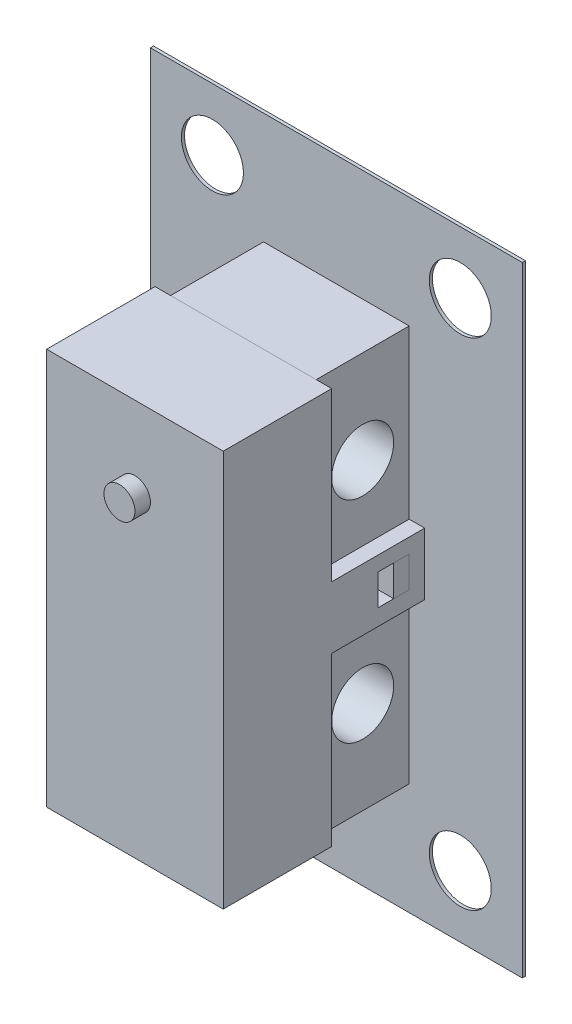
SolidWorks part; units mm, degrees
material "Plástico personalizado"
ref_plane "Alzado" through (0, 0, 0) normal (0, 0, 1) x (1, 0, 0)
ref_plane "Planta" through (0, 0, 0) normal (0, 1, 0) x (1, 0, 0)
ref_plane "Vista lateral" through (0, 0, 0) normal (1, 0, 0) x (0, 0, -1)
sketch "Sketch1" plane through (0, 0, 0) normal (0, 0, 1) x (1, 0, 0)
  line L1 (1.9718, 19.0836) -> (7.6718, 19.0836)
  line L2 (1.9718, 19.0836) -> (1.9718, 6.2836)
  line L3 (1.9718, 6.2836) -> (7.6718, 6.2836)
  line L4 (7.6718, 19.0836) -> (7.6718, 6.2836)
  dimension "D1" = 5.7
  dimension "D2" = 12.8
extrude "Boss-Extrude2" add sketch "Sketch1" along normal blind 6.5
sketch "Sketch3" plane through (0, 0, 6.5) normal (0, 0, 1) x (1, 0, 0)
  circle A0 centre (4.8218, 16.6018) radius 0.575
extrude "Boss-Extrude3" add sketch "Sketch3" along normal blind 0.5
sketch "Sketch7" plane through (7.6718, 0, 0) normal (1, 0, 0) x (0, 0, -1)
  line L0 (-6.5, 6.2836) -> (0, 6.2836) construction
  line L1 (0, 19.0836) -> (-3, 19.0836)
  line L2 (0, 19.0836) -> (0, 6.2836)
  line L3 (0, 6.2836) -> (-3, 6.2836)
  line L4 (-3, 19.0836) -> (-3, 6.2836)
  dimension "D1" = 3
extrude "Cut-Extrude1" cut sketch "Sketch7" against normal blind 0.5
sketch "Sketch8" plane through (1.9718, 0, 0) normal (-1, 0, 0) x (0, 0, 1)
  line L0 (6.5, 19.0836) -> (0, 19.0836) construction
  line L1 (0, 6.2836) -> (3, 6.2836)
  line L2 (0, 6.2836) -> (0, 19.0836)
  line L3 (0, 19.0836) -> (3, 19.0836)
  line L4 (3, 6.2836) -> (3, 19.0836)
  dimension "D1" = 3
extrude "Cut-Extrude2" cut sketch "Sketch8" against normal blind 0.5
sketch "Sketch9" plane through (7.1718, 0, 0) normal (1, 0, 0) x (0, 0, -1)
  line L0 (-3, 6.2836) -> (0, 6.2836) construction
  line L1 (0, 19.0836) -> (-3, 19.0836) construction
  circle A0 centre (-1.6614, 9.7836) radius 1
  circle A1 centre (-1.6614, 15.5836) radius 1
  dimension "D1" = 2
  dimension "D2" = 3.5
  dimension "D3" = 3.5
extrude "Cut-Extrude3" cut sketch "Sketch9" against normal through all
sketch "Sketch10" plane through (1.9718, 0, 0) normal (-1, 0, 0) x (0, 0, 1)
  line L0 (0, 12.6836) -> (6.5, 12.6836) construction
  line L1 (0, 19.0836) -> (0, 6.2836) construction
  line L2 (6.5, 19.0836) -> (6.5, 6.2836) construction
  line L3 (3, 6.2836) -> (3, 19.0836) construction
  line L4 (6, 11.6836) -> (0, 11.6836)
  line L5 (6, 11.6836) -> (6, 13.6836)
  line L6 (6, 13.6836) -> (0, 13.6836)
  line L7 (0, 11.6836) -> (0, 13.6836)
  line L8 (6, 11.6836) -> (0, 13.6836) construction
  line L9 (6, 13.6836) -> (0, 11.6836) construction
  point P6 (3, 12.6836)
  dimension "D1" = 2
extrude "Boss-Extrude4" add sketch "Sketch10" against normal blind 0.5
sketch "Sketch11" plane through (7.6718, 0, 0) normal (1, 0, 0) x (0, 0, -1)
  line L0 (-6.5, 12.6836) -> (0, 12.6836) construction
  line L1 (-6.5, 6.2836) -> (-6.5, 19.0836) construction
  line L2 (0, 6.2836) -> (0, 19.0836) construction
  line L3 (-3, 19.0836) -> (-3, 6.2836) construction
  line L4 (-6, 13.6836) -> (0, 13.6836)
  line L5 (-6, 13.6836) -> (-6, 11.6836)
  line L6 (-6, 11.6836) -> (0, 11.6836)
  line L7 (0, 13.6836) -> (0, 11.6836)
  line L8 (-6, 13.6836) -> (0, 11.6836) construction
  line L9 (-6, 11.6836) -> (0, 13.6836) construction
  point P6 (-3, 12.6836)
  dimension "D1" = 2
extrude "Boss-Extrude6" add sketch "Sketch11" against normal blind 0.5
sketch "Sketch13" plane through (0, 19.0836, 0) normal (0, 1, 0) x (1, 0, 0)
  line L1 (7.1718, -3) -> (2.4718, -3)
  line L2 (7.1718, -3) -> (7.1718, 0)
  line L3 (7.1718, 0) -> (2.4718, 0)
  line L4 (2.4718, -3) -> (2.4718, 0)
extrude "Cut-Extrude4" cut sketch "Sketch13" against normal through all
sketch "Sketch16" plane through (0, 19.0836, 0) normal (0, 1, 0) x (1, 0, 0)
  line L1 (2.4718, -3) -> (7.1718, -3)
  line L2 (2.4718, -3) -> (2.4718, 0)
  line L3 (2.4718, 0) -> (7.1718, 0)
  line L4 (7.1718, -3) -> (7.1718, 0)
extrude "Boss-Extrude8" add sketch "Sketch16" against normal blind 12.8 separate body
sketch "Sketch17" plane through (7.1718, 0, 0) normal (1, 0, 0) x (0, 0, -1)
  line L0 (-3, 19.0836) -> (0, 19.0836) construction
  line L1 (-3, 6.2836) -> (0, 6.2836) construction
  line L3 (0, 6.2836) -> (0, 19.0836) construction
  circle A0 centre (-1.5, 16.0836) radius 1
  circle A1 centre (-1.5, 9.2836) radius 1
  dimension "D1" = 3
  dimension "D2" = 3
  dimension "D3" = 1.5
extrude "Cut-Extrude5" cut sketch "Sketch17" against normal through all
sketch "Sketch18" plane through (0, 0, 7) normal (0, 0, 1) x (1, 0, 0)
  circle A0 centre (4.8218, 16.6018) radius 0.575
extrude "Cut-Extrude6" cut sketch "Sketch18" against normal up to surface (0.5 mm away) up to face at (5.3968, 16.6018, 6.5)
sketch "Sketch19" plane through (0, 0, 6.5) normal (0, 0, 1) x (1, 0, 0)
  circle A0 centre (4.8218, 16.4768) radius 0.5
extrude "Boss-Extrude9" add sketch "Sketch19" along normal blind 0.5 separate body
sketch "Sketch20" plane through (7.6718, 0, 0) normal (1, 0, 0) x (0, 0, -1)
  line L0 (0, 11.6836) -> (0, 13.6836) construction
  line L1 (-1.5, 13.2098) -> (-0.5, 13.2098)
  line L2 (-1.5, 13.2098) -> (-1.5, 12.2098)
  line L3 (-1.5, 12.2098) -> (-0.5, 12.2098)
  line L4 (-0.5, 13.2098) -> (-0.5, 12.2098)
  line L5 (-1.5, 13.2098) -> (-0.5, 12.2098) construction
  line L6 (-1.5, 12.2098) -> (-0.5, 13.2098) construction
  point P0 (-1, 12.7098)
  dimension "D1" = 1
  dimension "D2" = 1
  dimension "D3" = 0.5
extrude "Cut-Extrude8" cut sketch "Sketch20" against normal blind 0.5
sketch "Sketch21" plane through (7.1718, 0, 0) normal (1, 0, 0) x (0, 0, -1)
  line L0 (-1.5, 12.2098) -> (-0.5, 12.2098) construction
  line L1 (-0.5, 13.2098) -> (-1, 13.2098)
  line L2 (-0.5, 13.2098) -> (-0.5, 12.2098)
  line L3 (-0.5, 12.2098) -> (-1, 12.2098)
  line L4 (-1, 13.2098) -> (-1, 12.2098)
extrude "Boss-Extrude11" add sketch "Sketch21" along normal blind 0.5 separate body
sketch "Sketch22" plane through (1.9718, 0, 0) normal (-1, 0, 0) x (0, 0, 1)
  line L0 (0, 13.6836) -> (0, 11.6836) construction
  line L1 (0.5, 13.1392) -> (1.5, 13.1392)
  line L2 (0.5, 13.1392) -> (0.5, 12.1392)
  line L3 (0.5, 12.1392) -> (1.5, 12.1392)
  line L4 (1.5, 13.1392) -> (1.5, 12.1392)
  line L5 (0.5, 13.1392) -> (1.5, 12.1392) construction
  line L6 (0.5, 12.1392) -> (1.5, 13.1392) construction
  point P0 (1, 12.6392)
  dimension "D1" = 0.5
  dimension "D2" = 1
extrude "Cut-Extrude9" cut sketch "Sketch22" against normal blind 0.5
sketch "Sketch23" plane through (2.4718, 0, 0) normal (-1, 0, 0) x (0, 0, 1)
  line L0 (0.5, 12.1392) -> (1.5, 12.1392) construction
  line L1 (0.5, 13.1392) -> (1, 13.1392)
  line L2 (0.5, 13.1392) -> (0.5, 12.1392)
  line L3 (0.5, 12.1392) -> (1, 12.1392)
  line L4 (1, 13.1392) -> (1, 12.1392)
extrude "Boss-Extrude13" add sketch "Sketch23" along normal blind 0.5 separate body
sketch "Sketch28" plane through (0, 0, 0) normal (0, 0, -1) x (-1, 0, 0)
  line L0 (-7.1718, 19.0836) -> (-2.4718, 19.0836) construction
  line L1 (-10.8218, 22.6836) -> (1.1782, 22.6836)
  line L2 (-10.8218, 22.6836) -> (-10.8218, 2.6836)
  line L3 (-10.8218, 2.6836) -> (1.1782, 2.6836)
  line L4 (1.1782, 22.6836) -> (1.1782, 2.6836)
  line L5 (-7.1718, 6.2836) -> (-7.1718, 19.0836) construction
  point P6 (-4.8218, 19.0836)
  point P10 (-7.1718, 12.6836)
  dimension "D1" = 12
  dimension "D2" = 20
  dimension "D3" = 6
  dimension "D4" = 10
extrude "Boss-Extrude15" add sketch "Sketch28" along normal blind 0.1 separate body
sketch "Sketch29" plane through (0, 0, -0.1) normal (0, 0, -1) x (-1, 0, 0)
  line L0 (1.1782, 22.6836) -> (-10.8218, 22.6836) construction
  line L1 (-10.8218, 22.6836) -> (-10.8218, 2.6836) construction
  line L2 (-10.8218, 2.6836) -> (1.1782, 2.6836) construction
  line L3 (1.1782, 2.6836) -> (1.1782, 22.6836) construction
  circle A0 centre (-8.8218, 20.6836) radius 1
  circle A1 centre (-8.8218, 4.6836) radius 1
  circle A2 centre (-0.8218, 4.6836) radius 1
  circle A3 centre (-0.8218, 20.6836) radius 1
  dimension "D1" = 2
  dimension "D3" = 2
  dimension "D4" = 2
  dimension "D2" = 2
extrude "Cut-Extrude10" cut sketch "Sketch29" against normal blind 10.1
sketch "Sketch32" plane through (0, 6.2836, 0) normal (0, -1, 0) x (1, 0, 0)
  line L0 (4.3218, 7) -> (4.3218, 6.5) construction
  line L1 (1.9718, 6.5) -> (7.6718, 6.5) construction
  line L2 (4.3218, 7) -> (4.3218, 6.5) construction
